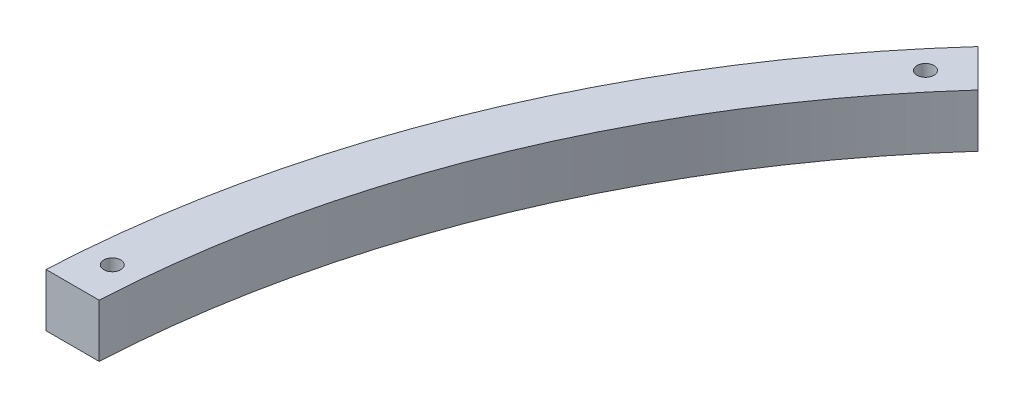
SolidWorks part; units mm, degrees
ref_plane "Front Plane" through (0, 0, 0) normal (0, 0, 1) x (1, 0, 0)
ref_plane "Top Plane" through (0, 0, 0) normal (0, 1, 0) x (1, 0, 0)
ref_plane "Right Plane" through (0, 0, 0) normal (1, 0, 0) x (0, 0, -1)
sketch "Sketch1" plane through (0, 0, 0) normal (0, 1, 0) x (1, 0, 0)
  line L1 (0, 200) -> (0, -200) construction
  line L6 (-200, 0) -> (200, 0) construction
  line L7 (-10, 199.7498) -> (-10, -199.7498) construction
  line L12 (-10, 199.7498) -> (-10, 189.7367)
  line L13 (-199.7498, 10) -> (199.7498, 10) construction
  line L14 (-199.7498, 10) -> (-189.7367, 10)
  line L15 (-141.4214, 141.4214) -> (141.4214, -141.4214) construction
  line L16 (-148.3155, 134.1734) -> (134.1734, -148.3155)
  arc A3 (-10, 199.7498) -> (-199.7498, 10) centre (0, 0) ccw
  arc A4 (-10, 189.7367) -> (-189.7367, 10) centre (0, 0) ccw
  arc A5 (-190, 0) -> (-189.7367, 10) centre (0, 0) ccw construction
  arc A6 (-200, 0) -> (-199.7498, 10) centre (0, 0) ccw construction
  circle A7 centre (0, 0) radius 195 construction
  dimension "D1" = 190
  dimension "D2" = 200
  dimension "D4" = 10
  dimension "D5" = 5
  dimension "D3" = 10
  dimension "D6" = 10
sketch "Sketch14" [suppressed] plane through (0, 0, 0) normal (0, 1, 0) x (1, 0, 0)
  line L0 (-200, 10) -> (200, 10) construction
  line L1 (-10, 200) -> (-10, -200) construction
  line L2 (-200, 10) -> (-189.7367, 10)
  line L3 (-10, 200) -> (-10, 189.7367)
  circle A0 centre (0, 0) radius 200 construction
  circle A1 centre (0, 0) radius 190 construction
  arc A2 (-10, 199.7498) -> (-199.7498, 10) centre (0, 0) ccw
  arc A3 (-10, 189.7367) -> (-189.7367, 10) centre (0, 0) ccw
sketch "roll" plane through (0, 0, 0) normal (0, 1, 0) x (1, 0, 0)
  line L0 (0, -195) -> (0, 195) construction
  dimension "D1" = 390
ref_axis "Axis1" through (0, -148.0362, 0) along (0, 1, 0)
extrude "base" add sketch "Sketch1" along normal mid plane 10 contours A4 L15 A3 L14 region at (-176.7216, 0, -73.2005)
sketch "Sketch25" plane through (0, 5, 0) normal (0, 1, 0) x (1, 0, 0)
  line L0 (-200, 0) -> (200, 0) construction
  line L1 (0, 200) -> (0, -200) construction
  line L2 (-200, 0) -> (200, 0)
  line L3 (0, 200) -> (0, -200)
  line L4 (0, 0) -> (-194.258, 16.9954) construction
  line L5 (0, 0) -> (-193.3317, 25.4526) construction
  line L6 (-141.4214, 141.4214) -> (141.4214, -141.4214) construction
  line L7 (-141.4214, 141.4214) -> (141.4214, -141.4214)
  line L8 (0, 0) -> (-149.3787, 125.3436) construction
  line L9 (0, 0) -> (-154.7039, 118.7085) construction
  circle A0 centre (0, 0) radius 195 construction
  circle A1 centre (0, 0) radius 195 construction
  dimension "D1" = 5
  dimension "D2" = 7.5
  dimension "D3" = 5
  dimension "D4" = 7.5
ref_plane "Plane1" through (0, 0, 0) normal (0.7071, 0, -0.7071) x (0.7071, 0, 0.7071)
hole_wizard "Ø3.2 (3.2) Diameter Hole1" positions "Sketch28" profile "Sketch29" hole size "Ø3.2" standard "ISO" end condition through all
sketch "Sketch28" plane through (0, 5, 0) normal (0, 1, 0) x (1, 0, 0)
  point P14 (-194.258, 16.9954)
  point P17 (-149.3787, 125.3436)
sketch "Sketch29" plane through (-194.258, 5, -16.9954) normal (1, 0, 0) x (0, 0, 1)
  line L0 (0, 0) -> (0, 10)
  line L1 (0, 10) -> (1.6, 10)
  line L2 (1.6, 10) -> (1.6, 0)
  line L5 (1.6, 0) -> (0, 0)
  line L11 (0, -6.35) -> (0, 107.95) construction
  dimension "Thru Hole Dia." = 3.2
  dimension "Thru Hole Depth" = 10
